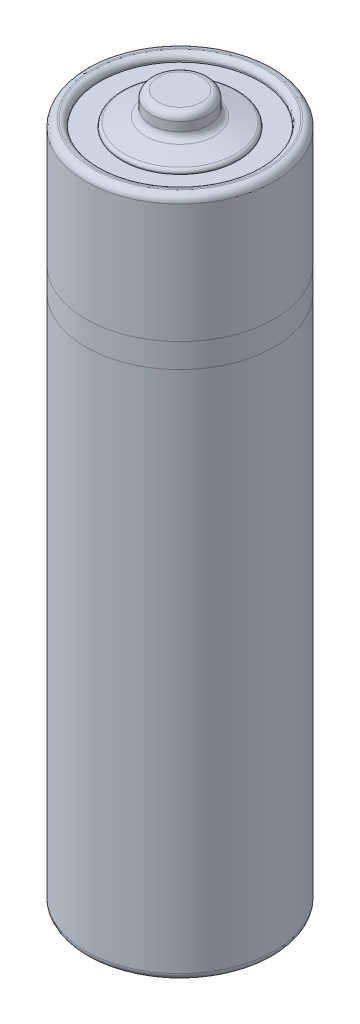
SolidWorks part; units mm, degrees
ref_plane "Front Plane" through (0, 0, 0) normal (0, 0, 1) x (1, 0, 0)
ref_plane "Top Plane" through (0, 0, 0) normal (0, 1, 0) x (1, 0, 0)
ref_plane "Right Plane" through (0, 0, 0) normal (1, 0, 0) x (0, 0, -1)
sketch "Sketch1" plane through (0, 0, 0) normal (0, 0, 1) x (1, 0, 0)
  line L0 (0, 54.3178) -> (0, -59.0133) construction
  line L1 (0, -24.425) -> (0.75, -24.425)
  line L2 (1.5, -24.175) -> (1.5, -24.525)
  line L3 (1.5, -24.525) -> (4.5, -24.525)
  line L4 (4.5, -24.525) -> (4.5, -24.025)
  line L5 (4.5, -24.025) -> (5.5, -24.025)
  line L6 (5.5, -24.025) -> (5.5, -24.325)
  line L7 (5.5, -24.325) -> (6.5, -24.325)
  line L8 (6.5, -24.325) -> (6.5, 22.675)
  line L9 (6.5, 22.675) -> (5.5, 22.675)
  line L10 (5.5, 22.675) -> (5.5, 22.175)
  line L11 (5.5, 22.175) -> (4, 22.175)
  line L12 (4, 22.175) -> (4, 22.425)
  line L13 (4, 22.425) -> (2, 22.925)
  line L14 (2, 22.925) -> (2, 24.425)
  line L15 (2, 24.425) -> (0, 24.425)
  line L16 (0, 24.425) -> (0, -24.425)
  line L17 (0.75, -24.425) -> (0.75, -24.175)
  line L18 (0.75, -24.175) -> (1.5, -24.175)
  dimension "D1" = 47
  dimension "D2" = 2
  dimension "D3" = 1.5
  dimension "D4" = 2
  dimension "D5" = 0.5
  dimension "D6" = 1
  dimension "D7" = 0.5
  dimension "D8" = 13
  dimension "D9" = 0.25
  dimension "D10" = 1
  dimension "D11" = 1
  dimension "D12" = 3
  dimension "D13" = 1.5
  dimension "D14" = 0.5
  dimension "D15" = 0.3
  dimension "D16" = 0.25
  dimension "D17" = 0.35
revolve "Revolve1" add sketch "Sketch1" angle 360 about L0
fillet "Fillet1" radius 0.5 1 edges at (0, 22.675, 6.5)
fillet "Fillet2" radius 0.4 1 edges at (0, 22.675, 5.5)
fillet "Fillet3" radius 0.25 1 edges at (0, 22.425, 4)
fillet "Fillet4" radius 0.5 1 edges at (0, 22.925, 2)
fillet "Fillet5" radius 0.5 1 edges at (0, 24.425, 2)
fillet "Fillet6" radius 0.5 1 edges at (0, -24.325, 6.5)
fillet "Fillet7" radius 0.3 1 edges at (0, -24.325, 5.5)
chamfer "Chamfer1" distance 0.5 angle 45 1 edges at (0, -24.525, 4.5)
chamfer "Chamfer2" distance 1 angle 45 1 edges at (0, -24.525, 1.5)
chamfer "Chamfer3" distance 0.25 angle 45 1 edges at (0, -24.175, 0.75)
sketch "Sketch3" plane through (0, 0, 0) normal (1, 0, 0) x (0, 0, -1)
  line B0 (-10.493, 12.2829) -> (12.801, 12.2829)
  line B1 (-10.493, 12.2829) -> (-10.493, 13.9515)
  line B2 (-10.493, 13.9515) -> (12.801, 13.9515)
  line B3 (12.801, 12.2829) -> (12.801, 13.9515)
sketch_block_instance "Block1-1"
sketch_block "Block1"
split line "Split Line2"
ref_plane "Plane1" through (0, 0, 6.5) normal (0, 0, 1) x (1, 0, 0)
